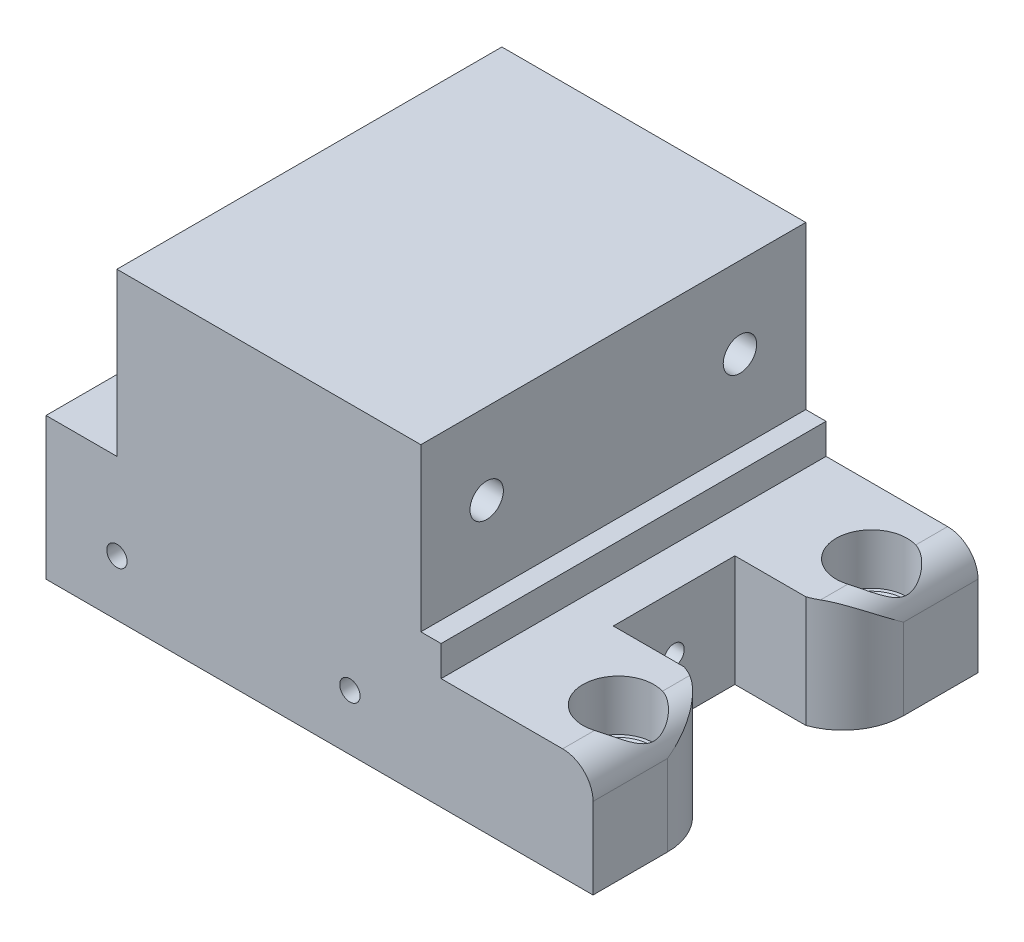
SolidWorks part; units mm, degrees
ref_plane "Спереди" through (0, 0, 0) normal (0, 0, 1) x (1, 0, 0)
ref_plane "Сверху" through (0, 0, 0) normal (0, 1, 0) x (1, 0, 0)
ref_plane "Справа" through (0, 0, 0) normal (1, 0, 0) x (0, 0, -1)
sketch "Эскиз6" [suppressed] plane through (0, 0, 0) normal (0, 1, 0) x (1, 0, 0)
  line L0 (-20, 0) -> (31, 0) construction
  line L1 (-20, -19) -> (31, -19)
  line L2 (-20, -19) -> (-20, 19)
  line L3 (-20, 19) -> (31, 19)
  line L4 (31, -19) -> (31, 19)
  line L5 (0, -19) -> (0, 19) construction
  dimension "D1" = 31
  dimension "D2" = 20
  dimension "D3" = 38
extrude "тело" [suppressed] add sketch "Эскиз6" along normal blind 11
sketch "Эскиз10" [suppressed] plane through (0, 11, 0) normal (0, 1, 0) x (1, 0, 0)
  circle A0 centre (0, 0) radius 10
  dimension "D1" = 20
extrude "основание оси" [suppressed] add sketch "Эскиз10" along normal blind 3
fillet "Скругление1" [suppressed] radius 3
sketch "Эскиз13" [suppressed] plane through (0, 0, 19) normal (0, 0, 1) x (1, 0, 0)
  line L0 (31, 5.5) -> (-13, 5.5) construction
  line L1 (31, 11) -> (31, 0) construction
  line L2 (0, 0) -> (0, 11) construction
  line L3 (-20, 11) -> (31, 11) construction
  circle A0 centre (-13, 5.5) radius 1.25
  circle A1 centre (13, 5.5) radius 1.25
  dimension "D1" = 2.5
  dimension "D2" = 26
  dimension "D3" = 18
extrude "отверстия под шурупы" [suppressed] cut sketch "Эскиз13" against normal through all
sketch "Эскиз15" [suppressed] plane through (0, 14, 0) normal (0, 1, 0) x (1, 0, 0)
  circle A0 centre (0, 0) radius 8.65
  dimension "D1" = 17.3
extrude "ось" [suppressed] add sketch "Эскиз15" along normal blind 13
sketch "Эскиз16" [suppressed] plane through (0, 27, 0) normal (0, 1, 0) x (1, 0, 0)
  line L0 (-7, 1.65) -> (-8.4912, 1.65) construction
  line L1 (-7, -1.65) -> (-8.4912, -1.65) construction
  line L2 (-1.65, 7) -> (-1.65, 8.4912)
  line L3 (1.65, 7) -> (1.65, 8.4912)
  line L4 (7, 1.65) -> (8.4912, 1.65) construction
  line L5 (7, -1.65) -> (8.4912, -1.65) construction
  line L6 (1.65, -7) -> (1.65, -8.4912)
  line L8 (-1.65, -7) -> (-1.65, -8.4912)
  circle A0 centre (0, 0) radius 7 construction
  arc A1 (-1.65, 7) -> (1.65, 7) centre (0, 7) ccw
  arc A2 (7, 1.65) -> (7, -1.65) centre (7, 0) ccw construction
  arc A3 (1.65, -7) -> (-1.65, -7) centre (0, -7) ccw
  arc A4 (-7, -1.65) -> (-7, 1.65) centre (-7, 0) ccw construction
  arc A5 (-8.4912, 1.65) -> (-8.4912, -1.65) centre (0, 0) ccw construction
  circle A6 centre (0, 0) radius 8.65 construction
  arc A7 (1.65, 8.4912) -> (-1.65, 8.4912) centre (0, 0) ccw
  arc A8 (8.4912, -1.65) -> (8.4912, 1.65) centre (0, 0) ccw construction
  arc A9 (-1.65, -8.4912) -> (1.65, -8.4912) centre (0, 0) ccw
  dimension "D1" = 14
  dimension "D2" = 1.65
extrude "крепление к серве" [suppressed] cut sketch "Эскиз16" against normal up to surface (13 mm away)
sketch "Эскиз26" [suppressed] plane through (0, 14, 0) normal (0, 1, 0) x (1, 0, 0)
  circle A0 centre (0, 7) radius 1.65
  circle A1 centre (0, -7) radius 1.65
  arc A2 (1.65, -7) -> (-1.65, -7) centre (0, -7) ccw construction
extrude "продолжение креплений" [suppressed] cut sketch "Эскиз26" against normal through all
chamfer "Фаска7" [suppressed] distance 2 angle 45
sketch "Эскиз17" [suppressed] plane through (0, 27, 0) normal (0, 1, 0) x (1, 0, 0)
  circle A0 centre (0, 0) radius 3
  dimension "D1" = 6
extrude "отверстие под болтик" [suppressed] cut sketch "Эскиз17" against normal through all
sketch "Эскиз24" [suppressed] plane through (0, 11, 0) normal (0, 1, 0) x (1, 0, 0)
  line L0 (31, 19) -> (-20, 19) construction
  line L1 (-15, 19) -> (15, 19)
  line L2 (-15, 19) -> (-15, -19)
  line L3 (-15, -19) -> (15, -19)
  line L4 (15, 19) -> (15, -19)
  line L5 (-20, -19) -> (31, -19) construction
  line L6 (0, 19) -> (0, -19) construction
  dimension "D1" = 30
extrude "крепление к арке" [suppressed] add sketch "Эскиз24" along normal blind 15
sketch "Эскиз27" [suppressed] plane through (-15, 0, 0) normal (-1, 0, 0) x (0, 0, 1)
  line L0 (0, 11) -> (0, 26) construction
  line L1 (-19, 11) -> (19, 11) construction
  line L2 (-19, 26) -> (19, 26) construction
  line L3 (-12.5, 18.5) -> (12.5, 18.5) construction
  circle A0 centre (-12.5, 18.5) radius 1.65
  circle A1 centre (12.5, 18.5) radius 1.65
  dimension "D2" = 3.3
  dimension "D1" = 25
  dimension "D3" = 7.5
extrude "отверстия под болты" [suppressed] cut sketch "Эскиз27" against normal through all
sketch "Эскиз19" [suppressed] plane through (0, 11, 0) normal (0, 1, 0) x (1, 0, 0)
  line L0 (15, -19) -> (31, -19) construction
  line L1 (37, 19) -> (23, 19)
  line L2 (37, 19) -> (37, -19)
  line L3 (37, -19) -> (23, -19)
  line L4 (23, 19) -> (23, -19)
  line L5 (31, 19) -> (31, -19) construction
  line L6 (31, -19) -> (31, 19) construction
  dimension "D1" = 6
  dimension "D2" = 8
extrude "выступ прикрутиться к колену" [suppressed] add sketch "Эскиз19" along normal blind 2
sketch "Эскиз20" [suppressed] plane through (0, 13, 0) normal (0, 1, 0) x (1, 0, 0)
  line L0 (34, 19) -> (34, -19) construction
  line L1 (37, 19) -> (23, 19) construction
  line L2 (23, -19) -> (37, -19) construction
  line L3 (37, -19) -> (37, 19) construction
  line L4 (23, 0) -> (37, 0) construction
  line L5 (23, 19) -> (23, -19) construction
  circle A0 centre (34, 10) radius 1.65
  circle A1 centre (34, -10) radius 1.65
  dimension "D3" = 3.3
  dimension "D1" = 3
  dimension "D2" = 20
extrude "шурупы сверху" [suppressed] cut sketch "Эскиз20" against normal through all
sketch "Эскиз23" [suppressed] plane through (0, 13, 0) normal (0, 1, 0) x (1, 0, 0)
  circle A0 centre (34, 10) radius 5
  circle A1 centre (34, -10) radius 5
  circle A2 centre (34, 10) radius 1.65
  circle A3 centre (34, -10) radius 1.65
  circle A4 centre (34, -10) radius 1.65 construction
  circle A5 centre (34, 10) radius 1.65 construction
  dimension "D1" = 10
extrude "наплывы" [suppressed] add sketch "Эскиз23" against normal up to surface (2 mm away)
chamfer "Фаска4" [suppressed] distance 1 angle 45
fillet "Скругление7" [suppressed] radius 3
chamfer "Фаска6" [suppressed] distance 1.5 angle 45
fillet "Скругление8" [suppressed] radius 0.5
sketch "Эскиз28" plane through (0, 0, 0) normal (0, 0, 1) x (1, 0, 0)
  line L0 (27, 0) -> (27, 11)
  line L5 (12, 14) -> (10, 14)
  line L6 (10, 14) -> (10, 30)
  line L7 (10, 30) -> (-20, 30)
  line L8 (-20, 30) -> (-20, 14)
  line L10 (-27, 11) -> (-27, 0)
  line L11 (-27, 0) -> (27, 0)
  line L12 (12, 11) -> (12, 14)
  line L13 (-27, 11) -> (-27, 14)
  line L14 (-27, 14) -> (-20, 14)
  line L15 (12, 11) -> (27, 11)
  circle A1 centre (3, 5.5) radius 1
  circle A2 centre (-20, 5.5) radius 1
  point P1 (0, 0)
  point P3 (0, 0)
  point P4 (25.5, 12.866)
  point P10 (-26.4655, 11)
  point P15 (0, 0)
  point P21 (-27.1074, 11)
  dimension "D6" = 2
  dimension "D9" = 2
  dimension "D2" = 30
  dimension "D3" = 11
  dimension "D4" = 54
  dimension "D5" = 7
  dimension "D7" = 14
  dimension "D8" = 23
  dimension "D10" = 5.5
  dimension "D14" = 16
  dimension "D15" = 3
  dimension "D16" = 7
extrude "Основа" add sketch "Эскиз28" along normal blind 38
sketch "Эскиз29" plane through (-20, 0, 0) normal (-1, 0, 0) x (0, 0, 1)
  line L0 (38, 30) -> (0, 30) construction
  line L1 (6.5, 22) -> (31.5, 22) construction
  line L2 (0, 30) -> (0, 14) construction
  circle A0 centre (6.5, 22) radius 1.65
  circle A1 centre (31.5, 22) radius 1.65
  point P4 (19, 22)
  point P5 (19, 30)
  point P11 (0, 22)
  dimension "D1" = 3.3
  dimension "D3" = 25
extrude "Отверстия под болты крепления к арке" cut sketch "Эскиз29" against normal up to next
sketch "Эскиз30" plane through (0, 11, 0) normal (0, 1, 0) x (1, 0, 0)
  line L0 (23, -13) -> (16, -13)
  line L1 (27, -7.3431) -> (27, -30.6569)
  line L2 (16, 0) -> (27, 0) construction
  line L3 (27, 0) -> (27, -7.3431) construction
  line L4 (27, -19) -> (-10.3281, -19) construction
  line L5 (16, 0) -> (16, -19) construction
  line L6 (23, 0) -> (23, -19) construction
  line L7 (16, -25) -> (16, -13)
  line L8 (23, -25) -> (16, -25)
  line L9 (-20, -38) -> (-20, 0) construction
  arc A0 (23, -13) -> (27, -7.3431) centre (21, -7.3431) ccw
  arc A1 (23, -25) -> (27, -30.6569) centre (21, -30.6569) cw
  point P15 (0, 0)
  point P19 (-20, -19)
  dimension "D3" = 6
  dimension "D1" = 11
  dimension "D2" = 4
  dimension "D4" = 12
extrude "Под шип" cut sketch "Эскиз30" against normal through all
fillet "Скругление9" radius 3 2 edges at (27, 11, 3.6716) (27, 11, 34.3284) tangent propagation no
sketch "Эскиз31" plane through (16, 0, 0) normal (1, 0, 0) x (0, 0, -1)
  line L0 (-13, 0) -> (-13, 11) construction
  line L1 (-38, 11) -> (0, 11) construction
  circle A0 centre (-19, 5.5) radius 1
  point P1 (0, 0)
  point P5 (-19, 11)
  point P8 (-19, 4.7309)
  point P9 (-13, 5.5)
  dimension "D1" = 2
extrude "Под шуруп торцевого шипа" cut sketch "Эскиз31" against normal blind 11
sketch "Эскиз32" plane through (0, 11, 0) normal (0, 1, 0) x (1, 0, 0)
  line L0 (2.376, -19) -> (16, -19) construction
  line L1 (16, -13) -> (16, -25) construction
  line L2 (23, -13) -> (16, -13) construction
  circle A0 centre (23, -6.5) radius 3.5
  circle A1 centre (23, -31.5) radius 3.5
  point P6 (0, 0)
  point P9 (16, -19)
  point P10 (19.4866, -5.8374)
  dimension "D1" = 7
  dimension "D2" = 7
  dimension "D3" = 6.5
extrude "Углубления под шляпки" cut sketch "Эскиз32" against normal blind 5
hole_wizard "Отв с зенковкой под крепление шипов" positions "Эскиз33" profile "Эскиз34" countersink size "M3" standard "DIN" end condition through all
sketch "Эскиз33" plane through (0, 6, 0) normal (0, 1, 0) x (1, 0, 0)
  point P0 (23, -6.5)
  point P2 (23, -31.5)
  point P5 (0, 0)
  point P8 (0, 0)
sketch "Эскиз34" plane through (23, 6, 6.5) normal (1, 0, 0) x (0, 0, 1)
  line L0 (0, 0) -> (0, 6)
  line L1 (0, 6) -> (1.7, 6)
  line L2 (1.7, 6) -> (1.7, 1.45)
  line L3 (1.7, 1.45) -> (3.15, 0)
  line L5 (3.15, 0) -> (0, 0)
  line L6 (-1.7, 1.45) -> (-3.15, 0) construction
  line L11 (0, -6.35) -> (0, 107.95) construction
  dimension "Диаметр сквозного отверстия" = 3.4
  dimension "Глубина сквозного отверстия" = 6
  dimension "Диаметр передней зенковки" = 6.3
  dimension "Угол передней зенковки" = 90
